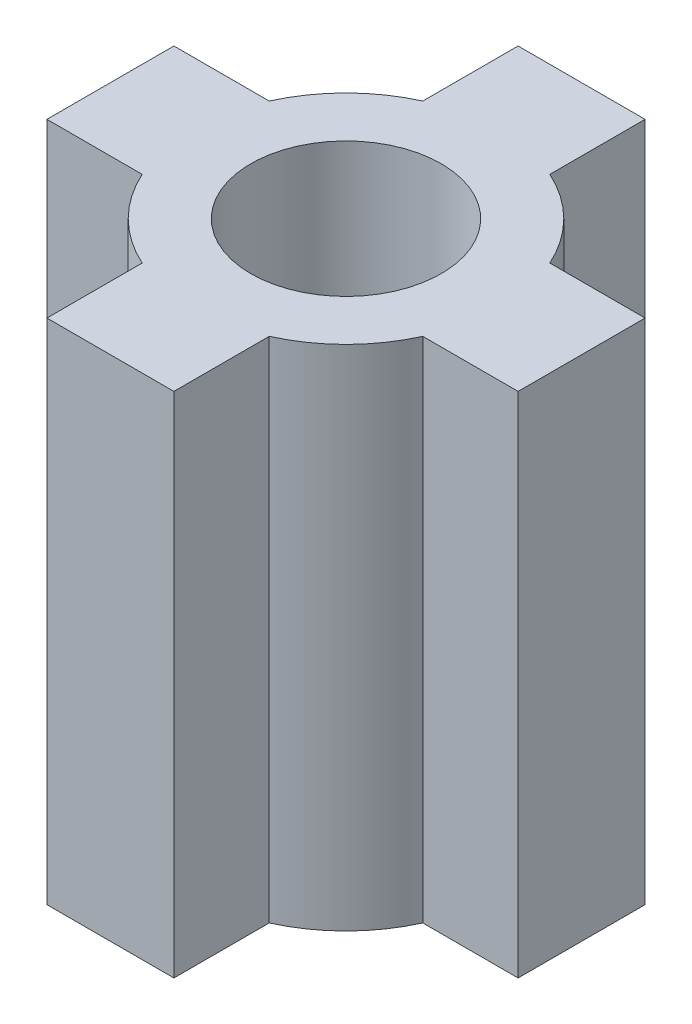
SolidWorks part; units mm, degrees
ref_plane "Front Plane" through (0, 0, 0) normal (0, 0, 1) x (1, 0, 0)
ref_plane "Top Plane" through (0, 0, 0) normal (0, 1, 0) x (1, 0, 0)
ref_plane "Right Plane" through (0, 0, 0) normal (1, 0, 0) x (0, 0, -1)
sketch "Sketch1" plane through (0, 0, 0) normal (0, 1, 0) x (1, 0, 0)
  circle A0 centre (0, 0) radius 2.425
  circle A1 centre (0, 0) radius 1.5
  dimension "D1" = 4.85
  dimension "D2" = 3
extrude "Boss-Extrude1" add sketch "Sketch1" along normal blind 8
sketch "Sketch2" plane through (0, 8, 0) normal (0, 1, 0) x (1, 0, 0)
  line L0 (0, 0) -> (-3.71, 0) construction
  line L1 (-3.71, -1) -> (-3.71, 1)
  line L2 (-3.71, 1) -> (-2.2092, 1)
  line L3 (-3.71, -1) -> (-2.2092, -1)
  circle A0 centre (0, 0) radius 2.425 construction
  arc A1 (-2.2092, -1) -> (-2.2092, 1) centre (0, 0) cw
  point P6 (-3.71, 0)
  point P11 (-0.9876, 0)
  point P12 (-0.6056, 0)
  point P13 (0, 0)
  dimension "D1" = 3.71
  dimension "D2" = 2
extrude "Boss-Extrude2" add sketch "Sketch2" against normal up to surface (8 mm away) up to face at (0, 0, 2.425)
pattern_circular "CirPattern1" count 4 over 360 about axis through (0, 8, 0) along (0, -1, 0) of "Boss-Extrude2"
sketch "Sketch3" plane through (0, 0, 0) normal (0, -1, 0) x (1, 0, 0)
  line L1 (-0.5385, -1.4) -> (0.5385, -1.4)
  circle A0 centre (0, 0) radius 1.5 construction
  arc A1 (0.5385, -1.4) -> (-0.5385, -1.4) centre (0, 0) cw
  point P1 (0, 0)
  point P3 (-0.0741, -0.2237)
  point P7 (0, -1.4)
  point P11 (0, -0.1218)
  dimension "D1" = 0.1
extrude "Boss-Extrude3" add sketch "Sketch3" against normal blind 1.25 contours L1 A1
fillet "Fillet1" radius 0.1 1 edges at (0, 1.25, -1.5)
